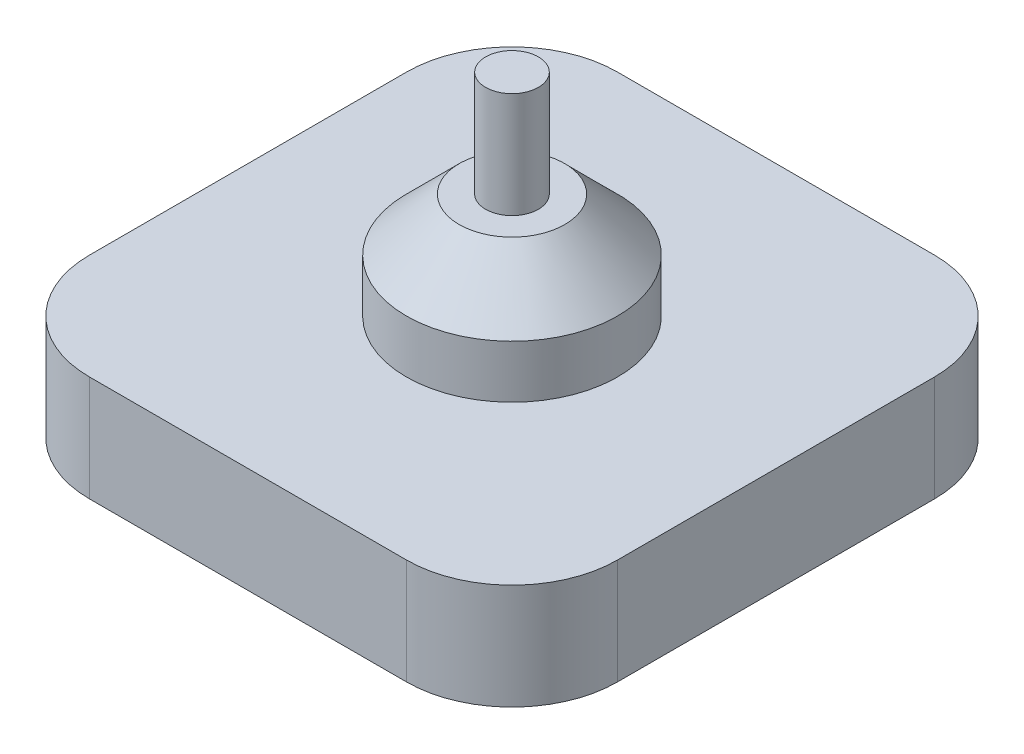
SolidWorks part; units mm, degrees
ref_plane "Front Plane" through (0, 0, 0) normal (0, 0, 1) x (1, 0, 0)
ref_plane "Top Plane" through (0, 0, 0) normal (0, 1, 0) x (1, 0, 0)
ref_plane "Right Plane" through (0, 0, 0) normal (1, 0, 0) x (0, 0, -1)
sketch "Sketch1" plane through (0, 0, 0) normal (0, 1, 0) x (1, 0, 0)
  line L1 (-250, 250) -> (250, 250)
  line L2 (-250, 250) -> (-250, -250)
  line L3 (-250, -250) -> (250, -250)
  line L4 (250, 250) -> (250, -250)
  line L5 (-250, 250) -> (250, -250) construction
  line L6 (-250, -250) -> (250, 250) construction
  point P0 (0, 0)
  dimension "D1" = 500
  dimension "D2" = 500
extrude "Boss-Extrude1" add sketch "Sketch1" along normal blind 100
sketch "Sketch2" plane through (0, 100, 0) normal (0, 1, 0) x (1, 0, 0)
  circle A0 centre (0, 0) radius 100
extrude "Boss-Extrude2" add sketch "Sketch2" along normal blind 100
sketch "Sketch3" plane through (0, 200, 0) normal (0, 1, 0) x (1, 0, 0)
  circle A0 centre (0, 0) radius 25
extrude "Boss-Extrude3" add sketch "Sketch3" along normal blind 100
chamfer "Chamfer1" distance 50 angle 45 1 edges at (0, 200, 100)
fillet "Fillet1" radius 100 4 edges at (250, 50, -250) (250, 50, 250) (-250, 50, -250) (-250, 50, 250)
ref_axis "Axis1" through (0, -15, 0) along (0, 1, 0)
ref_point "Point1"
